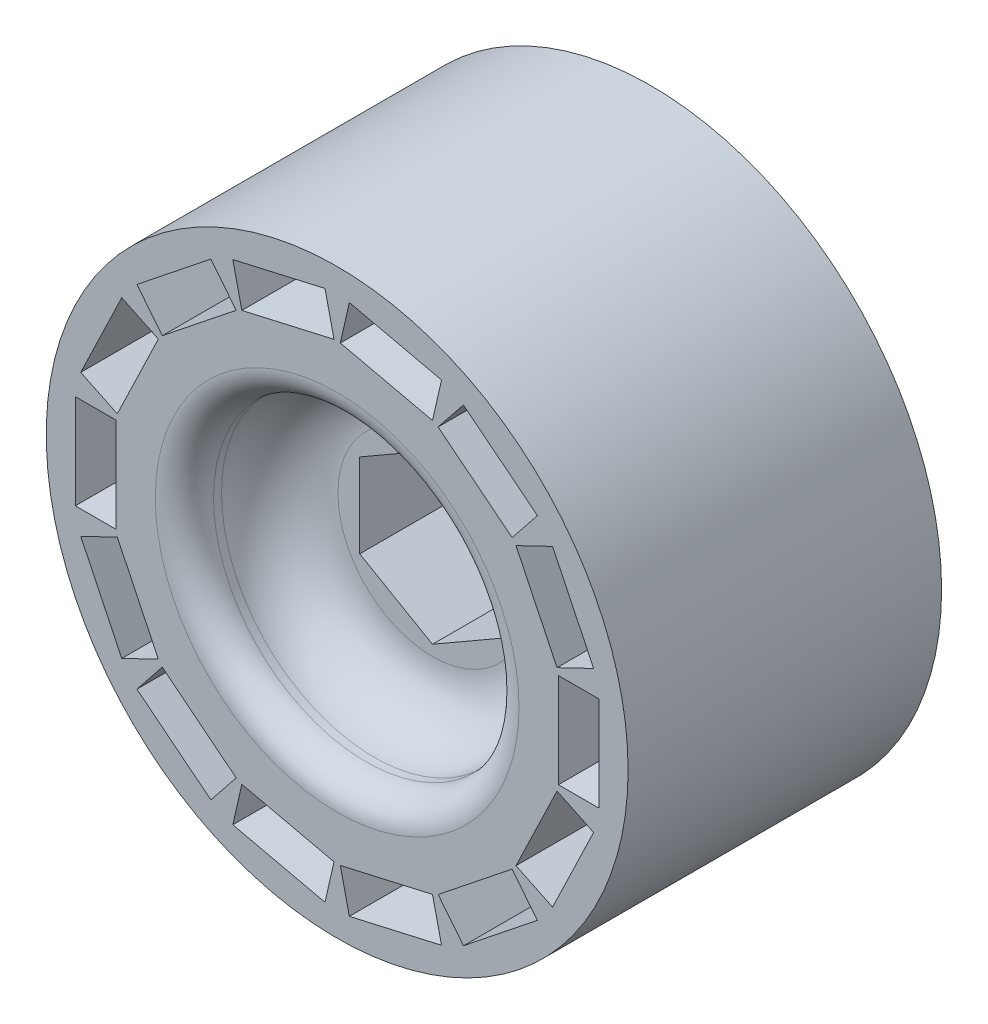
SolidWorks part; units mm, degrees
ref_plane "Front Plane" through (0, 0, 0) normal (0, 0, 1) x (1, 0, 0)
ref_plane "Top Plane" through (0, 0, 0) normal (0, 1, 0) x (1, 0, 0)
ref_plane "Right Plane" through (0, 0, 0) normal (1, 0, 0) x (0, 0, -1)
sketch "Sketch1" plane through (0, 0, 0) normal (0, 0, 1) x (1, 0, 0)
  circle A0 centre (-11.8226, 14.5298) radius 20
  circle A1 centre (-11.8226, 14.5298) radius 1
  dimension "D1" = 40
  dimension "D2" = 2
extrude "Boss-Extrude1" add sketch "Sketch1" along normal blind 21.55
hole_wizard "Tap Drill for M5x0.8 Tap1" positions "Sketch2" profile "Sketch3" hole size "M5x0.8" standard "ANSI Metric"
sketch "Sketch2" plane through (0, 0, 21.55) normal (0, 0, 1) x (1, 0, 0)
  point P0 (-11.8226, 14.5298)
sketch "Sketch3" plane through (-11.8226, 14.5298, 21.55) normal (1, 0, 0) x (0, -1, 0)
  line L0 (0, 0) -> (0, 6.2618)
  line L1 (0, 6.2618) -> (2.1, 5)
  line L2 (2.1, 5) -> (2.1, 0)
  line L5 (2.1, 0) -> (0, 0)
  line L10 (0, 6.2618) -> (-2.1, 5) construction
  line L11 (0, -6.35) -> (0, 107.95) construction
  dimension "Hole Dia." = 4.2
  dimension "Hole Depth" = 5
  dimension "Drill Angle" = 118
sketch "Sketch4" plane through (0, 0, 21.55) normal (0, 0, 1) x (1, 0, 0)
  line L1 (6.1774, 17.7798) -> (3.3874, 17.7798)
  line L2 (6.1774, 17.7798) -> (6.1774, 11.2798)
  line L3 (6.1774, 11.2798) -> (3.3874, 11.2798)
  line L4 (3.3874, 17.7798) -> (3.3874, 11.2798)
  circle A0 centre (-11.8226, 14.5298) radius 1 construction
  circle A1 centre (-11.8226, 14.5298) radius 20 construction
  dimension "D1" = 6.5
  dimension "D2" = 2.79
  dimension "D3" = 3.25
  dimension "D4" = 18
extrude "Cut-Extrude1" cut sketch "Sketch4" against normal offset from surface (19.05 mm away) 2.5 up to face at (8.1774, 14.5298, 0)
ref_axis "Axis1" through (-11.8226, 14.5298, 21.55) along (0, 0, -1)
pattern_circular "CirPattern1" count 14 over 360 about axis through (-11.8226, 14.5298, 21.55) along (0, 0, -1) of "Cut-Extrude1"
sketch "Sketch5" plane through (0, 0, 0) normal (0, 0, -1) x (-1, 0, 0)
  circle A0 centre (11.8226, 14.5298) radius 5
  circle A1 centre (11.8226, 14.5298) radius 6
  circle M2 centre (11.8226, 14.5298) radius 1
  dimension "D1" = 10
  dimension "D2" = 12
extrude "Cut-Extrude2" cut sketch "Sketch5" against normal blind 1 contours A1 A0 | A0 M2 region at (-6.964, 14.5298, 0) region at (-5.9923, 14.5298, 0)
sketch "Sketch6" plane through (0, 0, 21.55) normal (0, 0, 1) x (1, 0, 0)
  line L0 (-16.8226, 17.416) -> (-11.8226, 20.2957)
  line L1 (-6.8226, 11.6435) -> (-16.8226, 11.6435)
  line L2 (-6.8226, 11.6435) -> (-6.8226, 17.416)
  line L3 (-6.8226, 17.416) -> (-16.8226, 17.416)
  line L4 (-16.8226, 11.6435) -> (-16.8226, 17.416)
  line L5 (-6.8226, 11.6435) -> (-16.8226, 17.416) construction
  line L6 (-6.8226, 17.416) -> (-16.8226, 11.6435) construction
  line L7 (-11.8226, 20.2957) -> (-6.8226, 17.416)
  line L8 (-6.8226, 11.6435) -> (-11.8226, 8.7638)
  line L9 (-11.8226, 8.7638) -> (-16.8226, 11.6435)
  point P0 (-11.8226, 14.5298)
  dimension "D1" = 10
  dimension "D2" = 5.7725
  dimension "D3" = 5.77
  dimension "D4" = 5.77
  dimension "D5" = 5.77
  dimension "D6" = 5.77
extrude "Cut-Extrude3" cut sketch "Sketch6" against normal up to surface (21.55 mm away) contours L4 L1 L2 L3 | L7 L0 L3 | L9 L8 L1 region at (-11.8226, 18.3759, 21.55) region at (-11.8226, 14.5298, 21.55) region at (-11.8226, 10.6836, 21.55) up to face at (-17.8226, 14.5298, 0)
sketch "Sketch7" plane through (0, 0, 21.55) normal (0, 0, 1) x (1, 0, 0)
  circle A0 centre (-11.8226, 14.5298) radius 10.5
  dimension "D1" = 21
extrude "Cut-Extrude4" cut sketch "Sketch7" against normal offset from surface (6.55 mm away) 15 up to face at (-17.8226, 14.5298, 0)
fillet "Fillet4" radius 2 1 edges at (-1.3226, 14.5298, 21.55)
fillet "Fillet5" radius 4 1 edges at (-1.3226, 14.5298, 15)
equation "\"D2@Sketch4\"=2.79"
equation "\"D3@Sketch4\"=6.5/2"
equation "\"oringdiameter\"= 11"
equation "\"oringthickness\"= 2"
equation "\"D2@Sketch5\"=\"oringdiameter\" + \"oringthickness\"/2"
equation "\"D1@Sketch5\"=\"oringdiameter\" - \"oringthickness\"/2"
equation "\"D1@Cut-Extrude2\"= \"oringthickness\"/2"
equation "\"D1@Boss-Extrude1\"= 2.5 + (25.4*3/4)"
equation "\"D2@Sketch6\"=4.618*10/8"
